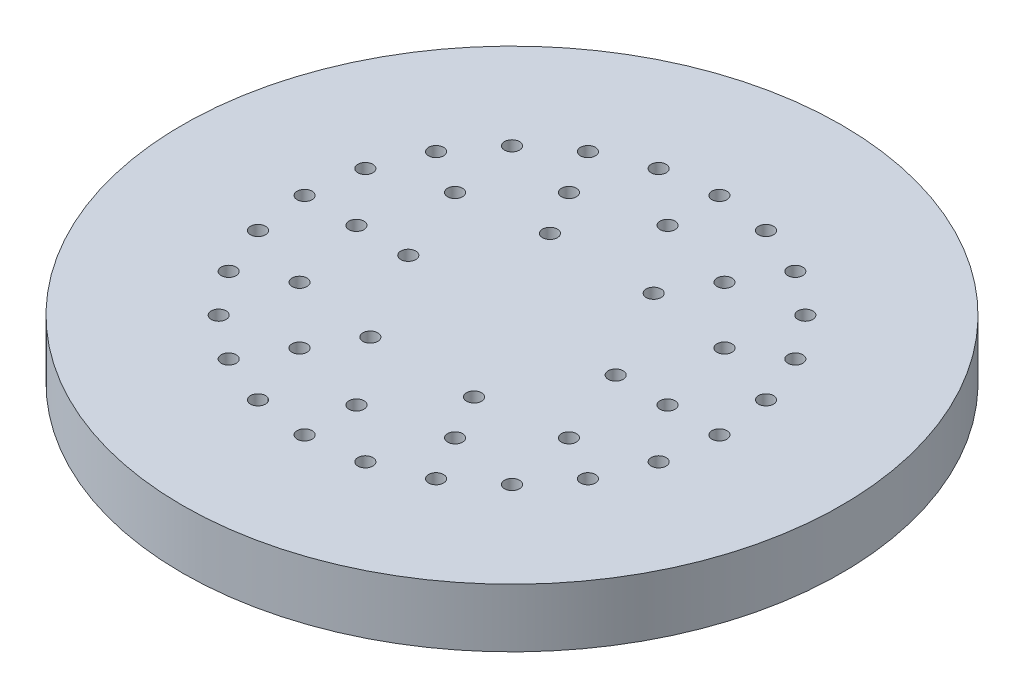
SolidWorks part; units mm, degrees
material "AISI 304"
ref_plane "Front Plane" through (0, 0, 0) normal (0, 0, 1) x (1, 0, 0)
ref_plane "Top Plane" through (0, 0, 0) normal (0, 1, 0) x (1, 0, 0)
ref_plane "Right Plane" through (0, 0, 0) normal (1, 0, 0) x (0, 0, -1)
ref_axis "Axial" through (0, -55, 0) along (0, 1, 0)
ref_plane "Bottom Plane" through (0, -5.08, 0) normal (0, 1, 0) x (1, 0, 0)
sketch "Sketch1" plane through (0, 0, 0) normal (0, 1, 0) x (1, 0, 0)
  circle A0 centre (0, 0) radius 28.575
  dimension "D1" = 57.15
extrude "Billet" add sketch "Sketch1" against normal blind 5.08
sketch "Sketch2" plane through (0, 0, 0) normal (0, 1, 0) x (1, 0, 0)
  line L0 (0, 18.6449) -> (0, -20.0163) construction
  line L1 (-17.698, 0) -> (15.8694, 0) construction
  circle A0 centre (8.9916, 0) radius 0.6477
  circle A1 centre (13.4874, 0) radius 0.6477
  circle A2 centre (17.9832, 0) radius 0.6477
  dimension "D1" = 1.2954
  dimension "D2" = 8.9916
  dimension "D3" = 4.4958
  dimension "D4" = 4.4958
extrude "First Lox Hole" cut sketch "Sketch2" against normal through all
pattern_circular "CirPattern1" count 6 over 360 about axis through (0, -55, 0) along (0, 1, 0) of "First Lox Hole"
pattern_circular "CirPattern2" count 12 over 360 about axis through (0, -55, 0) along (0, 1, 0) skipping 2, 4, 6, 8, 10 of face at (13.4874, -5.08, 0.6477)
pattern_circular "CirPattern3" count 24 over 360 about axis through (0, -55, 0) along (0, 1, 0) skipping 4, 8, 12, 16, 20 of face at (17.9832, -5.08, 0.6477)
sketch "Sketch4" plane through (0, -5.08, 0) normal (0, 1, 0) x (1, 0, 0)
  line L0 (0, 30.8778) -> (0, -33.3039) construction
  line L1 (-2.794, 0) -> (2.794, 0) construction
  circle A0 centre (0, 25.4) radius 1.1906
  circle A1 centre (0, -25.4) radius 1.1906
  dimension "D1" = 2.3813
  dimension "D2" = 25.4
extrude "Dowel" cut sketch "Sketch4" along normal blind 3.175
